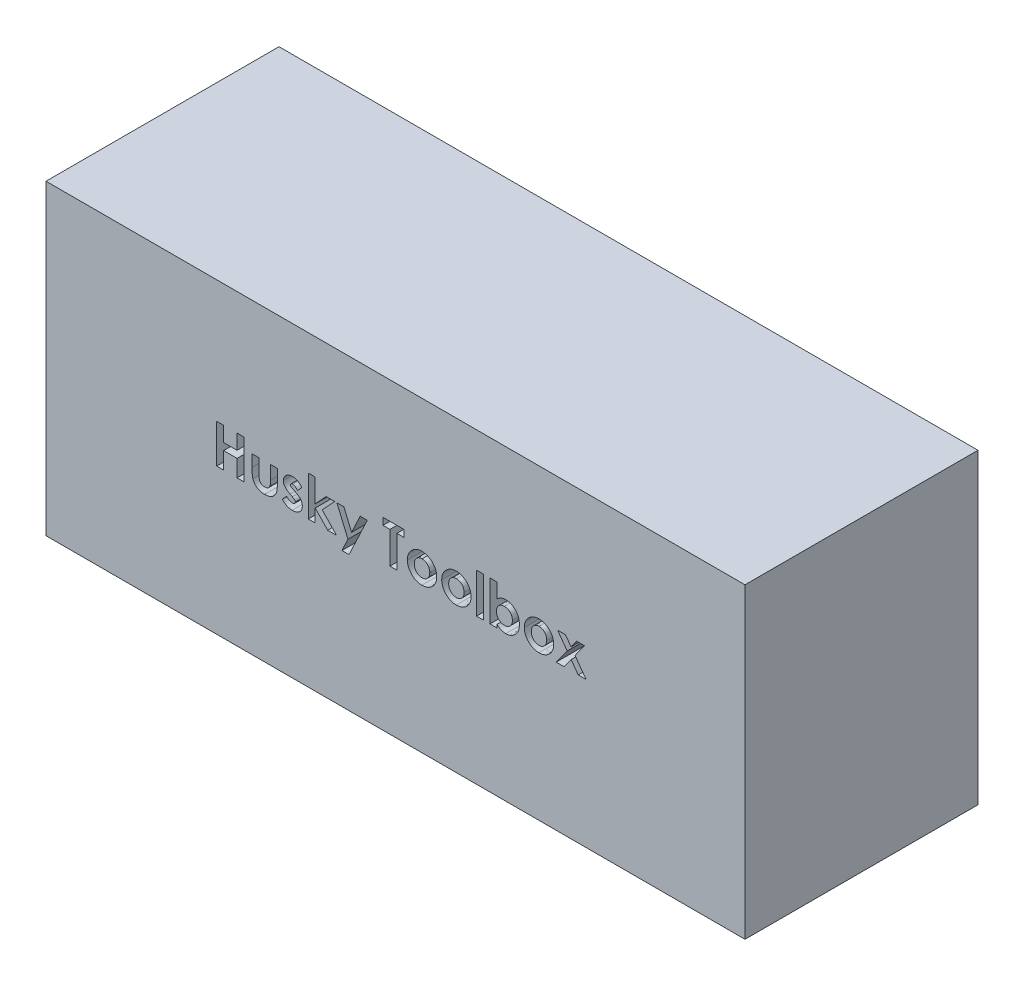
SolidWorks part; units mm, degrees
ref_plane "Front Plane" through (0, 0, 0) normal (0, 0, 1) x (1, 0, 0)
ref_plane "Top Plane" through (0, 0, 0) normal (0, 1, 0) x (1, 0, 0)
ref_plane "Right Plane" through (0, 0, 0) normal (1, 0, 0) x (0, 0, -1)
sketch "Sketch1" plane through (0, 0, 0) normal (0, 1, 0) x (1, 0, 0)
  line L1 (-914.4, -304.8) -> (914.4, -304.8)
  line L2 (-914.4, -304.8) -> (-914.4, 304.8)
  line L3 (-914.4, 304.8) -> (914.4, 304.8)
  line L4 (914.4, -304.8) -> (914.4, 304.8)
  line L5 (-914.4, -304.8) -> (914.4, 304.8) construction
  line L6 (-914.4, 304.8) -> (914.4, -304.8) construction
  point P0 (0, 0)
  dimension "D1" = 1828.8
  dimension "D2" = 609.6
extrude "Boss-Extrude1" add sketch "Sketch1" along normal blind 803.275
sketch "Sketch2" plane through (0, 0, 304.8) normal (0, 0, 1) x (1, 0, 0)
  line L0 (-914.4, 0) -> (914.4, 0) construction
  text T0 "<b>Husky Toolbox</b>" font "Century Gothic" height 101.6
  dimension "D1" = 381
extrude "Cut-Extrude1" cut sketch "Sketch2" against normal blind 76.2
